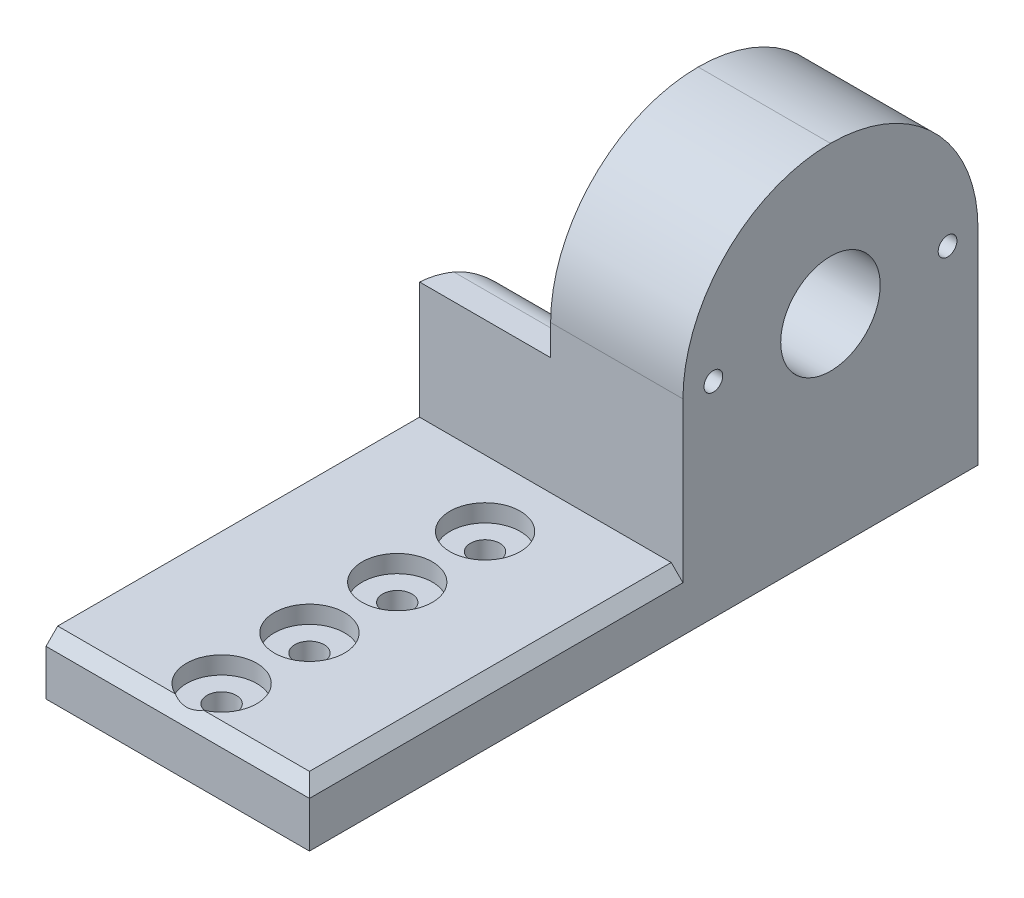
SolidWorks part; units mm, degrees
ref_plane "Front Plane" through (0, 0, 0) normal (0, 0, 1) x (1, 0, 0)
ref_plane "Top Plane" through (0, 0, 0) normal (0, 1, 0) x (1, 0, 0)
ref_plane "Right Plane" through (0, 0, 0) normal (1, 0, 0) x (0, 0, -1)
sketch "Sketch1" plane through (0, 0, 0) normal (0, 1, 0) x (1, 0, 0)
  line L1 (0, 0) -> (57.15, 0)
  line L2 (0, 0) -> (0, 145.034)
  line L3 (0, 145.034) -> (57.15, 145.034)
  line L4 (57.15, 0) -> (57.15, 145.034)
  dimension "D1" = 57.15
  dimension "D2" = 145.034
extrude "Boss-Extrude1" add sketch "Sketch1" along normal blind 25.4
sketch "Sketch3" plane through (57.15, 0, 0) normal (1, 0, 0) x (0, 0, -1)
  line L0 (0, 0) -> (145.034, 0) construction
  line L1 (145.034, 25.4) -> (145.034, 0) construction
  circle A0 centre (113.03, 44.45) radius 32.004
  dimension "D1" = 64.008
  dimension "D2" = 44.45
  dimension "D3" = 32.004
sketch "Sketch4" plane through (0, 0, 0) normal (0, -1, 0) x (-1, 0, 0)
  line L0 (0, 0) -> (-57.15, 0) construction
  line L1 (-57.15, 0) -> (-57.15, 145.034) construction
  circle A0 centre (-28.575, 9.525) radius 3.175
  circle A1 centre (-28.575, 28.575) radius 3.175
  circle A2 centre (-28.575, 47.625) radius 3.175
  circle A3 centre (-28.575, 66.675) radius 3.175
  dimension "D1" = 6.35
  dimension "D2" = 6.35
  dimension "D3" = 6.35
  dimension "D4" = 6.35
  dimension "D5" = 19.05
  dimension "D6" = 19.05
  dimension "D7" = 19.05
  dimension "D8" = 9.525
  dimension "D9" = 28.575
  dimension "D10" = 28.575
  dimension "D11" = 28.575
  dimension "D12" = 28.575
extrude "Cut-Extrude3" cut sketch "Sketch4" against normal through all
sketch "Sketch7" plane through (0, 0, 0) normal (0, -1, 0) x (1, 0, 0)
  line L0 (57.15, 0) -> (57.15, -145.034) construction
  line L1 (57.15, -81.026) -> (28.448, -81.026)
  line L2 (57.15, -81.026) -> (57.15, -145.034)
  line L3 (57.15, -145.034) -> (28.448, -145.034)
  line L4 (28.448, -81.026) -> (28.448, -145.034)
  line L8 (57.15, -145.034) -> (0, -145.034) construction
  dimension "D1" = 28.702
  dimension "D2" = 64.008
  dimension "D3" = 0
extrude "Boss-Extrude2" add sketch "Sketch7" against normal blind 76.454
fillet "Fillet1" radius 32.004 2 edges at (42.799, 76.454, -145.034) (42.799, 76.454, -81.026)
sketch "Sketch9" plane through (28.448, 0, 0) normal (-1, 0, 0) x (0, 0, 1)
  circle A1 centre (-113.03, 44.45) radius 10.795
  circle A2 centre (-138.43, 44.45) radius 2.032
  circle A3 centre (-87.63, 44.45) radius 2.032
  dimension "D1" = 21.59
  dimension "D4" = 4.064
  dimension "D5" = 4.064
  dimension "D2" = 25.4
  dimension "D3" = 25.4
  dimension "D6" = 32.004
  dimension "D7" = 32.004
  dimension "D8" = 32.004
  dimension "D9" = 32.004
extrude "Cut-Extrude5" cut sketch "Sketch9" against normal blind 76.454
sketch "Sketch10" plane through (0, 25.4, 0) normal (0, 1, 0) x (1, 0, 0)
  line L2 (28.448, 113.03) -> (28.448, 81.026)
  line L3 (50.8, 0) -> (0, 0)
  line L4 (0, 113.03) -> (0, 0)
  line L5 (57.15, 81.026) -> (28.448, 81.026)
  line L6 (57.15, 81.026) -> (57.15, 0)
  line L7 (57.15, 0) -> (50.8, 0)
  line L8 (28.448, 145.034) -> (0, 145.034)
  line L9 (28.448, 145.034) -> (28.448, 113.03)
  line L11 (0, 145.034) -> (0, 113.03)
extrude "Cut-Extrude7" cut sketch "Sketch10" against normal blind 12.954
sketch "Sketch11" plane through (0, 12.446, 0) normal (0, 1, 0) x (1, 0, 0)
  circle A0 centre (28.575, 66.675) radius 7.62
  circle A1 centre (28.575, 47.625) radius 7.62
  circle A2 centre (28.575, 28.575) radius 7.62
  circle A3 centre (28.575, 9.525) radius 7.62
  dimension "D1" = 15.24
  dimension "D2" = 15.24
  dimension "D3" = 15.24
  dimension "D4" = 15.24
extrude "Cut-Extrude8" cut sketch "Sketch11" against normal blind 3.81
chamfer "Chamfer1" distance 2.54 angle 45 2 edges at (28.575, 12.446, 0) (57.15, 12.446, -40.513)
sketch "Sketch14" plane through (28.448, 0, 0) normal (-1, 0, 0) x (0, 0, 1)
  line L0 (-113.0527, 43.294) -> (-113.03, 44.45) construction
  line L1 (-113.03, 44.45) -> (-113.6572, 12.4521) construction
  line L2 (-81.026, 44.45) -> (-81.026, 12.446) construction
  line L3 (-113.6374, 13.462) -> (-125.3969, 13.462) construction
  line L4 (-145.034, 12.446) -> (-2.54, 12.446) construction
  line L5 (-113.6374, 13.462) -> (-138.0214, 37.846)
  line L6 (-113.6374, 13.462) -> (-89.2534, 37.846)
  line L7 (-113.6374, 13.462) -> (-106.3908, 13.462) construction
  line L8 (-81.026, 12.446) -> (-145.034, 12.446) construction
  line L9 (-138.0214, 37.846) -> (-145.034, 37.846)
  line L10 (-145.034, 44.45) -> (-145.034, 12.446) construction
  line L11 (-145.034, 37.846) -> (-145.034, 12.446)
  line L12 (-145.034, 12.446) -> (-81.026, 12.446)
  line L13 (-81.026, 12.446) -> (-81.026, 37.846)
  line L14 (-81.026, 37.846) -> (-89.2534, 37.846)
  circle A0 centre (-113.03, 44.45) radius 32.004 construction
  dimension "D1" = 1.123
  dimension "D2" = 1.016
  dimension "D3" = 45
  dimension "D4" = 45
  dimension "D5" = 25.4
  dimension "D6" = 25.4
extrude "Boss-Extrude4" add sketch "Sketch14" along normal up to surface (28.448 mm away) up to face at (0, 6.9596, -58.5216)
fillet "Fillet3" radius 6.35 4 edges at (0, 25.654, -101.4454) (0, 25.654, -125.8294) (14.224, 37.846, -89.2534) (14.224, 37.846, -138.0214)
